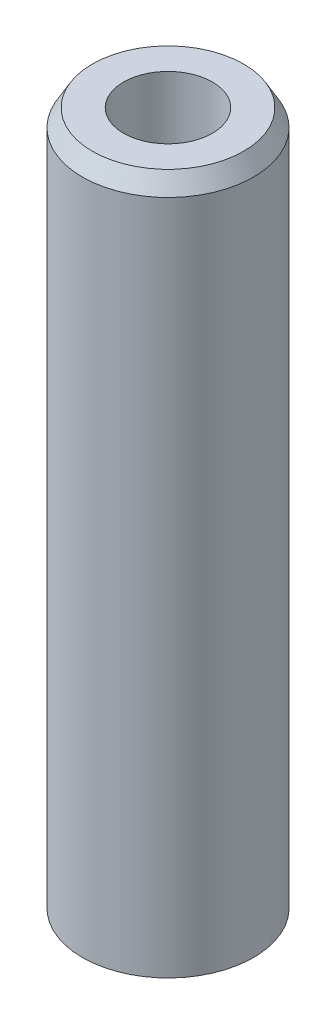
SolidWorks part; units mm, degrees
ref_plane "Front Plane" through (0, 0, 0) normal (0, 0, 1) x (1, 0, 0)
ref_plane "Top Plane" through (0, 0, 0) normal (0, 1, 0) x (1, 0, 0)
ref_plane "Right Plane" through (0, 0, 0) normal (1, 0, 0) x (0, 0, -1)
sketch "Sketch1" plane through (0, 0, 0) normal (0, 1, 0) x (1, 0, 0)
  circle A0 centre (0, 0) radius 25
  dimension "SHAFT_OD" = 50
extrude "Boss-Extrude1" add sketch "Sketch1" along normal blind 205.3603
sketch "Sketch2" plane through (0, 0, 0) normal (0, 1, 0) x (1, 0, 0)
  circle A0 centre (0, 0) radius 12.9684
  dimension "BORE_D" = 25.9368
extrude "Cut-Extrude1" cut sketch "Sketch2" along normal through all
chamfer "Chamfer1" distance 5.0551 angle 30 2 edges at (0, 205.3603, 25) (0, 0, 25) first distance on face at (0, 205.3603, 25) first distance on face at (0, 0, 12.9684)
